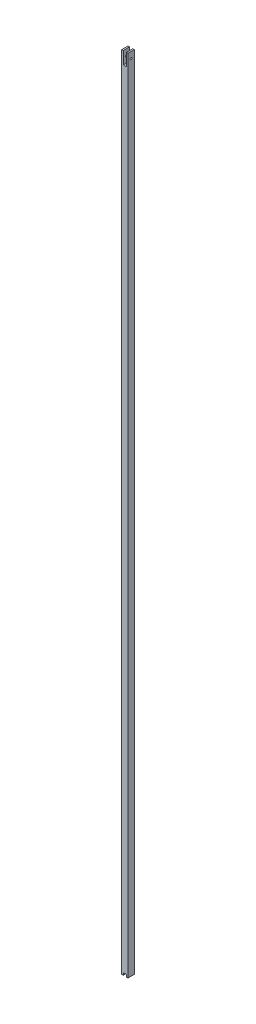
SolidWorks part; units mm, degrees
material "Plain Carbon Steel"
ref_plane "Front Plane" through (0, 0, 0) normal (0, 0, 1) x (1, 0, 0)
ref_plane "Top Plane" through (0, 0, 0) normal (0, 1, 0) x (1, 0, 0)
ref_plane "Right Plane" through (0, 0, 0) normal (1, 0, 0) x (0, 0, -1)
sketch "Sketch1" plane through (0, 0, 0) normal (0, 0, 1) x (1, 0, 0)
  line L0 (0, 0) -> (1.5875, 0)
  line L1 (1.5875, 0) -> (1.5875, 2.3812)
  line L2 (1.5875, 2.3812) -> (4.7625, 2.3812)
  line L3 (4.7625, 2.3812) -> (4.7625, 0)
  line L4 (4.7625, 0) -> (6.35, 0)
  line L5 (6.35, 0) -> (6.35, 812.8)
  line L6 (6.35, 812.8) -> (4.7625, 812.8)
  line L7 (4.7625, 812.8) -> (4.7625, 800.1)
  line L8 (4.7625, 800.1) -> (1.5875, 800.1)
  line L9 (1.5875, 800.1) -> (1.5875, 812.8)
  line L10 (1.5875, 812.8) -> (0, 812.8)
  line L11 (0, 812.8) -> (0, 0)
  dimension "D1" = 1.5875
  dimension "D2" = 2.3812
  dimension "D3" = 3.175
  dimension "D4" = 2.3812
  dimension "D5" = 1.5875
  dimension "D6" = 812.8
  dimension "D7" = 1.5875
  dimension "D8" = 12.7
  dimension "D9" = 3.175
  dimension "D10" = 12.7
extrude "Boss-Extrude1" add sketch "Sketch1" along normal blind 6.35
sketch "Sketch2" plane through (0, 0, 0) normal (1, 0, 0) x (0, 0, -1)
  circle A0 centre (3.175, 806.45) radius 1
  dimension "D3" = 2
  dimension "D1" = 3.175
  dimension "D2" = 806.45
sketch "Sketch3" plane through (0, 0, 0) normal (1, 0, 0) x (0, 0, -1)
  circle A0 centre (-3.175, 806.45) radius 1
  dimension "D3" = 2
  dimension "D1" = 3.175
  dimension "D2" = 806.45
extrude "Cut-Extrude3" cut sketch "Sketch3" against normal mid plane 20
ref_plane "Plane1" through (0, 806.45, 0) normal (0, 1, 0) x (1, 0, 0)
ref_plane "Plane2" through (0, 0, 3.175) normal (0, 0, 1) x (1, 0, 0)
ref_axis "Axis1" through (6.6675, 806.45, 3.175) along (-1, 0, 0)
ref_plane "Plane3" through (0, 0, 3.175) normal (0, 0, 1) x (1, 0, 0)
ref_axis "Axis2" through (6.6675, 0, 3.175) along (-1, 0, 0)
